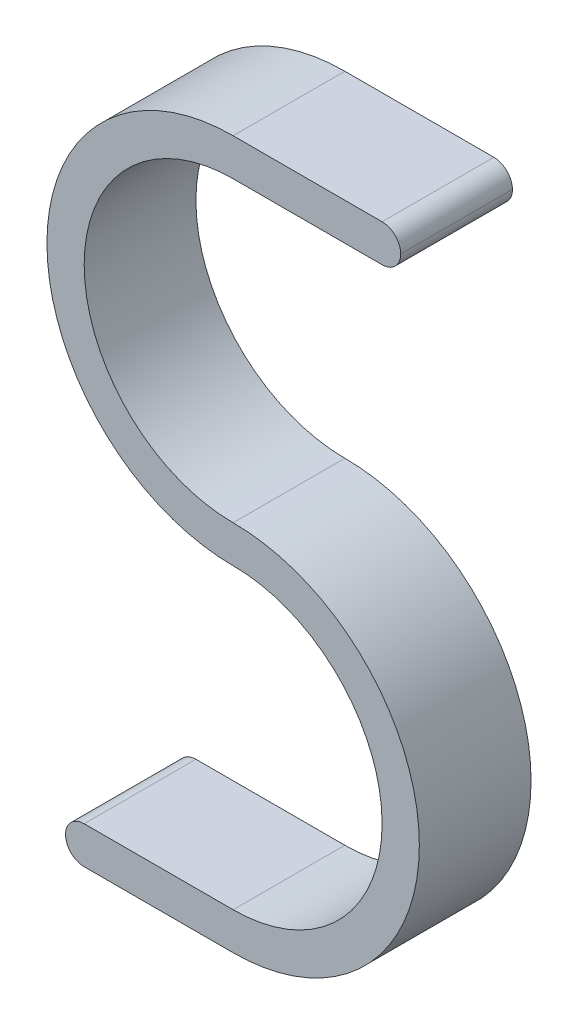
SolidWorks part; units mm, degrees
ref_plane "Front Plane" through (0, 0, 0) normal (0, 0, 1) x (1, 0, 0)
ref_plane "Top Plane" through (0, 0, 0) normal (0, 1, 0) x (1, 0, 0)
ref_plane "Right Plane" through (0, 0, 0) normal (1, 0, 0) x (0, 0, -1)
sketch "Sketch1" plane through (0, 0, 0) normal (0, 0, 1) x (1, 0, 0)
  line L0 (4.5698, 56.5223) -> (27.0698, 56.5223)
  line L1 (27.0698, 56.5223) -> (27.0698, 51.5223)
  line L2 (27.0698, 51.5223) -> (4.5698, 51.5223)
  line L3 (4.5698, -38.4777) -> (-17.9302, -38.4777)
  line L4 (-17.9302, -38.4777) -> (-17.9302, -33.4777)
  line L5 (-17.9302, -33.4777) -> (4.5698, -33.4777)
  arc A0 (4.5698, 51.5223) -> (4.5698, 11.5223) centre (4.5698, 31.5223) ccw
  arc A1 (4.5698, -33.4777) -> (4.5698, 6.5223) centre (4.5698, -13.4777) ccw
  arc A2 (4.5698, 56.5223) -> (4.5698, 6.5223) centre (4.5698, 31.5223) ccw
  arc A3 (4.5698, -38.4777) -> (4.5698, 11.5223) centre (4.5698, -13.4777) ccw
  point P6 (0, 0)
  point P8 (0, 0)
  dimension "D1" = 40
  dimension "D2" = 40
  dimension "D3" = 50
  dimension "D4" = 50
  dimension "D5" = 95
  dimension "D6" = 22.5
  dimension "D7" = 22.5
  dimension "D8" = 40
  dimension "D9" = 50
extrude "Boss-Extrude1" add sketch "Sketch1" along normal blind 15
fillet "Fillet1" radius 2.5 4 edges at (-17.9302, -38.4777, 7.5) (-17.9302, -33.4777, 7.5) (27.0698, 51.5223, 7.5) (27.0698, 56.5223, 7.5)
